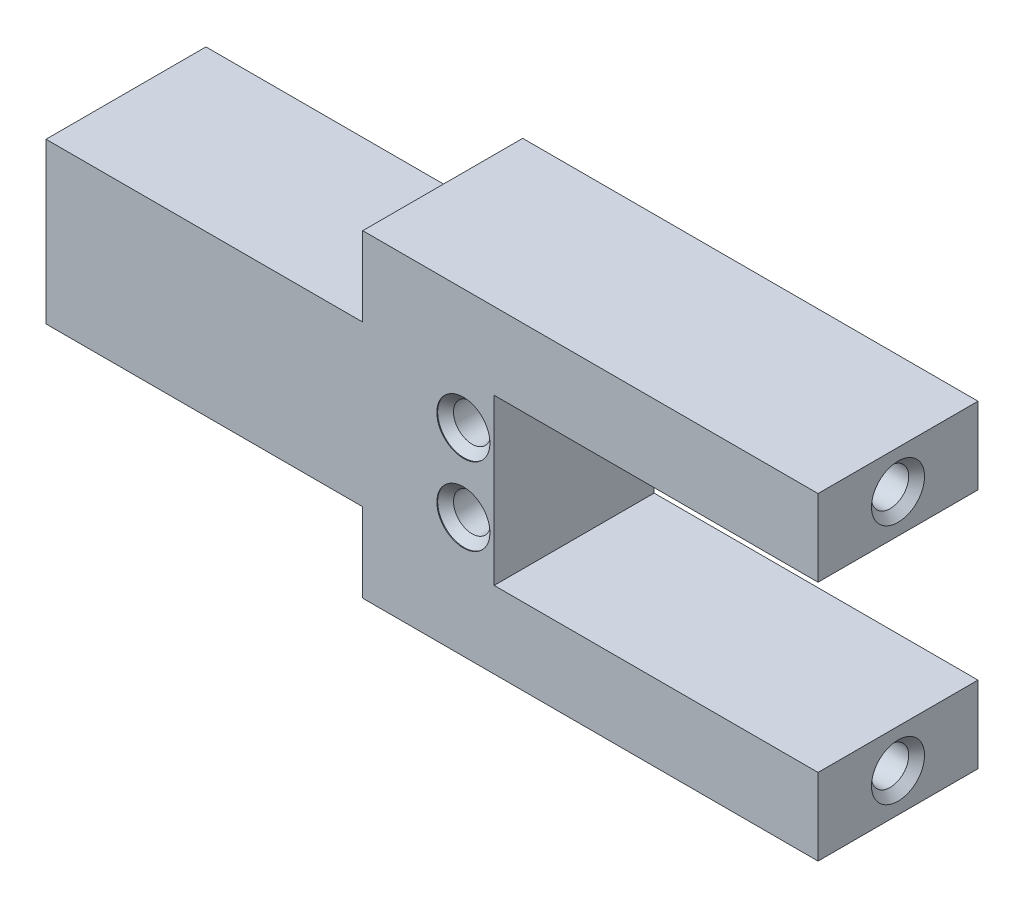
SolidWorks part; units mm, degrees
ref_plane "Front Plane" through (0, 0, 0) normal (0, 0, 1) x (1, 0, 0)
ref_plane "Top Plane" through (0, 0, 0) normal (0, 1, 0) x (1, 0, 0)
ref_plane "Right Plane" through (0, 0, 0) normal (1, 0, 0) x (0, 0, -1)
sketch "Sketch1" plane through (0, 0, 0) normal (1, 0, 0) x (0, 0, -1)
  line L1 (-10, 10) -> (10, 10)
  line L2 (-10, 10) -> (-10, -10)
  line L3 (-10, -10) -> (10, -10)
  line L4 (10, 10) -> (10, -10)
  line L5 (-10, 10) -> (10, -10) construction
  line L6 (-10, -10) -> (10, 10) construction
  point P0 (0, 0)
  dimension "D1" = 20
  dimension "D2" = 20
extrude "Boss-Extrude1" add sketch "Sketch1" along normal blind 20
sketch "Sketch2" plane through (20, 0, 0) normal (1, 0, 0) x (0, 0, -1)
  line L1 (-10, 20.1) -> (10, 20.1)
  line L2 (-10, 20.1) -> (-10, -20.1)
  line L3 (-10, -20.1) -> (10, -20.1)
  line L4 (10, 20.1) -> (10, -20.1)
  line L5 (-10, 20.1) -> (10, -20.1) construction
  line L6 (-10, -20.1) -> (10, 20.1) construction
  point P0 (0, 0)
  dimension "D1" = 20
  dimension "D2" = 40.2
extrude "Boss-Extrude2" add sketch "Sketch2" along normal blind 64.7
sketch "Sketch3" plane through (0, 0, 10) normal (0, 0, 1) x (1, 0, 0)
  line L1 (20, 20.1) -> (84.7, 20.1) construction
  line L2 (20, 20.1) -> (20, -20.1) construction
  line L3 (20, -20.1) -> (84.7, -20.1) construction
  line L4 (84.7, 20.1) -> (84.7, -20.1) construction
  line L5 (20, 20.1) -> (84.7, -20.1) construction
  line L6 (20, -20.1) -> (84.7, 20.1) construction
  line L7 (72.8, 10.4) -> (31.9, 10.4)
  line L8 (72.8, 10.4) -> (72.8, -10.4)
  line L9 (72.8, -10.4) -> (31.9, -10.4)
  line L10 (31.9, 10.4) -> (31.9, -10.4)
  line L11 (72.8, 10.4) -> (31.9, -10.4) construction
  line L12 (72.8, -10.4) -> (31.9, 10.4) construction
  point P4 (52.35, 0)
  point P7 (52.35, 0)
  dimension "D1" = 40.9
  dimension "D2" = 20.8
extrude "Cut-Extrude1" cut sketch "Sketch3" against normal through all
sketch "Sketch4" plane through (0, 0, 10) normal (0, 0, 1) x (1, 0, 0)
  line L0 (84.7, -20.1) -> (20, -20.1) construction
  line L1 (84.7, 20.1) -> (72.8, 20.1)
  line L2 (84.7, 20.1) -> (84.7, -20.1)
  line L3 (84.7, -20.1) -> (72.8, -20.1)
  line L4 (72.8, 20.1) -> (72.8, -20.1)
  line L5 (84.7, 20.1) -> (72.8, -20.1) construction
  line L6 (84.7, -20.1) -> (72.8, 20.1) construction
  point P4 (78.75, 0)
extrude "Cut-Extrude2" cut sketch "Sketch4" against normal through all
sketch "Sketch5" plane through (0, 0, 10) normal (0, 0, 1) x (1, 0, 0)
  line L0 (31.9, 0) -> (28.53, 0) construction
  line L5 (31.9, 10.4) -> (31.9, -10.4) construction
  line L7 (25.16, 0) -> (25.86, 0) construction
  line L8 (25.16, 9.4) -> (31.9, 9.4) construction
  line L9 (25.16, 9.4) -> (25.16, -9.4) construction
  line L10 (25.16, -9.4) -> (31.9, -9.4) construction
  line L11 (31.9, 9.4) -> (31.9, -9.4) construction
  line L12 (25.16, 9.4) -> (31.9, -9.4) construction
  line L13 (25.16, -9.4) -> (31.9, 9.4) construction
  line L14 (25.86, 0) -> (30.16, 0) construction
  line L15 (28.01, 0) -> (28.01, 9.4) construction
  line L16 (28.53, 9.4) -> (28.53, 7.1) construction
  line L17 (28.53, 7.1) -> (28.53, 2.7) construction
  line L18 (28.53, 2.7) -> (28.53, -2.7) construction
  line L19 (28.53, -2.7) -> (28.53, -7.1) construction
  line L20 (28.53, -7.1) -> (28.53, -9.4) construction
  line L21 (28.53, 4.9) -> (28.01, 4.9) construction
  circle A0 centre (28.01, 4.9) radius 2.35
  circle A1 centre (28.01, -4.9) radius 2.35
  dimension "D9" = 4.7
  dimension "D1" = 3.37
  dimension "D2" = 18.8
  dimension "D3" = 0.7
  dimension "D4" = 4.3
  dimension "D5" = 2.3
  dimension "D6" = 4.4
  dimension "D7" = 2.3
  dimension "D8" = 4.4
extrude "Cut-Extrude3" cut sketch "Sketch5" against normal blind 10
sketch "Sketch6" plane through (72.8, 0, 0) normal (1, 0, 0) x (0, 0, -1)
  line L0 (10, -10.4) -> (10, 10.4) construction
  line L1 (10, 0) -> (-3.0961, 0) construction
  line L3 (10, -10.4) -> (-10, -10.4) construction
  line L4 (10, -10.4) -> (10, -20.1) construction
  line L5 (10, -20.1) -> (-10, -20.1) construction
  line L6 (-10, -10.4) -> (-10, -20.1) construction
  line L7 (10, -10.4) -> (-10, -20.1) construction
  line L8 (10, -20.1) -> (-10, -10.4) construction
  circle A0 centre (0, -15.25) radius 2.35
  circle A1 centre (0, 15.25) radius 2.35
  point P10 (0, -15.25)
  dimension "D1" = 4.7
extrude "Cut-Extrude4" cut sketch "Sketch6" against normal blind 10
chamfer "Chamfer1" distance 1 angle 45 4 edges at (30.36, 4.9, 10) (25.66, -4.9, 10) (72.8, 15.25, 2.35) (72.8, -15.25, -2.35)
sketch "Sketch7" plane through (20, 0, 0) normal (-1, 0, 0) x (0, 0, 1)
  line L1 (10, 20.1) -> (-10, 20.1)
  line L2 (10, 20.1) -> (10, 10)
  line L3 (10, 10) -> (-10, 10)
  line L4 (-10, 20.1) -> (-10, 10)
  line L5 (10, 20.1) -> (-10, 10) construction
  line L6 (10, 10) -> (-10, 20.1) construction
  line L7 (10, -10) -> (-10, -10)
  line L8 (10, -10) -> (10, -20.1)
  line L9 (10, -20.1) -> (-10, -20.1)
  line L10 (-10, -10) -> (-10, -20.1)
  line L11 (10, -10) -> (-10, -20.1) construction
  line L12 (10, -20.1) -> (-10, -10) construction
  point P4 (0, 15.05)
  point P11 (0, -15.05)
extrude "Boss-Extrude4" add sketch "Sketch7" along normal blind 4.7
sketch "Sketch9" plane through (0, 0, 0) normal (-1, 0, 0) x (0, 0, 1)
  line L1 (10, 10) -> (-10, 10)
  line L2 (10, 10) -> (10, -10)
  line L3 (10, -10) -> (-10, -10)
  line L4 (-10, 10) -> (-10, -10)
  line L5 (10, 10) -> (-10, -10) construction
  line L6 (10, -10) -> (-10, 10) construction
  point P4 (0, 0)
extrude "Boss-Extrude5" add sketch "Sketch9" along normal blind 24.7
sketch "Sketch10" plane through (-24.7, 0, 0) normal (-1, 0, 0) x (0, 0, 1)
  circle A0 centre (0, 0) radius 3
  dimension "D1" = 6
extrude "Cut-Extrude5" cut sketch "Sketch10" against normal blind 2
fillet "Fillet1" radius 3.23 1 edges at (-22.7, 0, 3)
sketch "Sketch11" plane through (-24.7, 0, 0) normal (-1, 0, 0) x (0, 0, 1)
  line L5 (-10, -10) -> (10, -10)
  line L6 (-10, -10) -> (-10, 10)
  line L7 (-10, 10) -> (10, 10)
  line L8 (10.1, -10.1) -> (10.1, 10.1)
  line L9 (10.1, 10.1) -> (-10.1, 10.1)
  line L10 (-10.1, 10.1) -> (-10.1, -10.1)
  line L11 (-10.1, -10.1) -> (10.1, -10.1)
  line L12 (10.1, -10.1) -> (10.1, 10.1)
  line L13 (10.1, 10.1) -> (-10.1, 10.1)
  line L14 (-10.1, 10.1) -> (-10.1, -10.1)
  line L15 (-10.1, -10.1) -> (10.1, -10.1)
  line L16 (10, -10) -> (10, 10)
  line L17 (-10, -10) -> (10, 10) construction
  line L18 (-10, 10) -> (10, -10) construction
  point P4 (0, 0)
  dimension "D1" = 0.1
extrude "Boss-Extrude6" add sketch "Sketch11" against normal up to surface (40 mm away) up to face at (15.3, 15.05, 0)
sketch "Sketch12" plane through (0, 0, 10) normal (0, 0, 1) x (1, 0, 0)
  line L0 (72.8, 20.1) -> (15.3, 20.1)
  line L1 (15.3, 20.1) -> (15.3, -20.1)
  line L2 (15.3, -20.1) -> (72.8, -20.1)
  line L3 (72.8, -20.1) -> (72.8, -10.4)
  line L4 (72.8, -10.4) -> (31.9, -10.4)
  line L5 (31.9, -10.4) -> (31.9, 10.4)
  line L6 (31.9, 10.4) -> (72.8, 10.4)
  line L7 (72.8, 10.4) -> (72.8, 20.1)
  circle A1 centre (28.01, 4.9) radius 3.35
  circle A2 centre (28.01, -4.9) radius 3.35
extrude "Boss-Extrude7" add sketch "Sketch12" along normal blind 0.1
sketch "Sketch13" plane through (0, 0, -10) normal (0, 0, -1) x (-1, 0, 0)
  line L0 (-72.8, -20.1) -> (-15.3, -20.1)
  line L1 (-15.3, -20.1) -> (-15.3, 20.1)
  line L2 (-15.3, 20.1) -> (-72.8, 20.1)
  line L3 (-72.8, 20.1) -> (-72.8, 10.4)
  line L4 (-72.8, 10.4) -> (-31.9, 10.4)
  line L5 (-31.9, 10.4) -> (-31.9, -10.4)
  line L6 (-31.9, -10.4) -> (-72.8, -10.4)
  line L7 (-72.8, -10.4) -> (-72.8, -20.1)
extrude "Boss-Extrude8" add sketch "Sketch13" along normal blind 0.1
